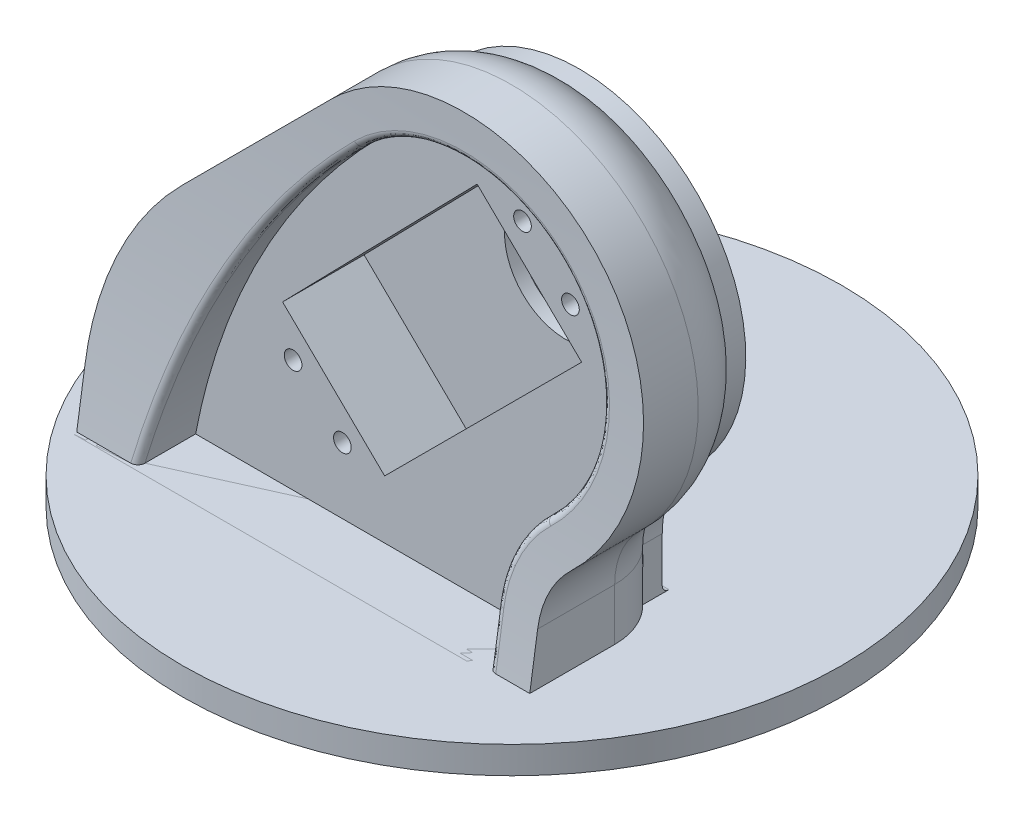
SolidWorks part; units mm, degrees
ref_plane "前视基准面" through (0, 0, 0) normal (0, 0, 1) x (1, 0, 0)
ref_plane "上视基准面" through (0, 0, 0) normal (0, 1, 0) x (1, 0, 0)
ref_plane "右视基准面" through (0, 0, 0) normal (1, 0, 0) x (0, 0, -1)
sketch "草图1" plane through (0, 0, 0) normal (0, 1, 0) x (1, 0, 0)
  line L0 (-7.25, 0) -> (14.0729, 0)
  circle A0 centre (0, 0) radius 48.5
  circle A1 centre (-7.25, 0) radius 1.5
  circle A2 centre (7.25, 0) radius 1.5
  dimension "D1" = 97
  dimension "D2" = 3
  dimension "D3" = 3
  dimension "D4" = 14.5
  dimension "D5" = 7.25
extrude "凸台-拉伸1" add sketch "草图1" along normal blind 4 contours A0 A2 A1 region at (-47.1282, 0, 0)
sketch "草图2" plane through (0, 0, 0) normal (0, -1, 0) x (1, 0, 0)
  circle A0 centre (0, 0) radius 3.75
  dimension "D1" = 7.5
extrude "切除-拉伸1" cut sketch "草图2" against normal blind 1.5
ref_plane "基准面1" through (0, 0, 4) normal (0, 0, 1) x (1, 0, 0)
sketch "草图3" plane through (0, 0, 4) normal (0, 0, 1) x (1, 0, 0)
  line L1 (-34.5671, 4) -> (-34.5671, 11.86)
  line L2 (48.5, 4) -> (-48.5, 4) construction
  line L3 (-24.2495, 36.7687) -> (-3.4141, 57.6041)
  line L5 (26.1129, 4) -> (-34.5671, 4)
  line L6 (26.1129, 11.64) -> (26.1129, 4)
  arc A0 (-34.5671, 11.86) -> (-24.2495, 36.7687) centre (0.6592, 11.86) cw
  arc A1 (-3.4141, 57.6041) -> (30.7827, 22.5159) centre (13.91, 40.28) cw
  arc A2 (30.7827, 22.5159) -> (26.1129, 11.64) centre (41.1129, 11.64) ccw
  circle A3 centre (13.91, 40.28) radius 9
  dimension "D6" = 24.5
  dimension "D7" = 15
  dimension "D9" = 18
  dimension "D1" = 7.86
  dimension "D2" = 7.64
  dimension "D3" = 40.28
  dimension "D4" = 13.91
  dimension "D5" = 45
  dimension "D8" = 60.68
extrude "凸台-拉伸2" add sketch "草图3" along normal blind 14
ref_plane "基准面2" through (0, 0, 6) normal (0, 0, 1) x (1, 0, 0)
sketch "草图4" plane through (0, 0, 6) normal (0, 0, 1) x (1, 0, 0)
  line L0 (12.8696, 56.5659) -> (28.25, 41.5516)
  line L1 (12.8696, 56.5659) -> (-15.7705, 27.2274)
  line L2 (28.25, 41.5516) -> (-0.7435, 12.5581)
  line L3 (-15.7705, 27.2274) -> (-0.7435, 12.5581)
  line L4 (12.8696, 56.5659) -> (13.2313, 41.5516) construction
  line L5 (13.2313, 41.5516) -> (28.25, 41.5516) construction
  line L6 (13.2313, 41.5516) -> (20.5598, 49.0587) construction
  line L7 (48.5, 4) -> (-48.5, 4) construction
  line L8 (19.5465, 55.1785) -> (26.6025, 48.091) construction
  line L9 (20.5598, 49.0587) -> (24.743, 53.3439) construction
  line L10 (-1.4504, 41.8967) -> (13.7532, 27.0548) construction
  circle A0 centre (19.5465, 55.1785) radius 1.3
  circle A1 centre (26.6025, 48.091) radius 1.3
  circle A2 centre (-6.9674, 13.7026) radius 1.3
  circle A3 centre (-14.2228, 20.5859) radius 1.3
  point P13 (23.0745, 51.6348)
  dimension "D8" = 2.6
  dimension "D9" = 2.6
  dimension "D1" = 91.38
  dimension "D2" = 45
  dimension "D3" = 41
  dimension "D4" = 21
  dimension "D5" = 5
  dimension "D6" = 5
  dimension "D7" = 3.6
extrude "切除-拉伸2" cut sketch "草图4" along normal through all
sketch "草图5" plane through (0, 0, 18) normal (0, 0, 1) x (1, 0, 0)
  line L0 (-5.5354, 59.7254) -> (-26.3708, 38.89)
  line L1 (-37.5671, 11.86) -> (-37.5671, 1)
  line L2 (-37.5671, 1) -> (29.1129, 1)
  line L3 (29.1129, 1) -> (29.1129, 6.5935)
  line L4 (-34.5671, 4) -> (26.1129, 4)
  line L5 (26.1129, 4) -> (26.1129, 11.64)
  line L6 (-3.4141, 57.6041) -> (-24.2495, 36.7687)
  line L7 (-34.5671, 11.86) -> (-34.5671, 4)
  line L8 (-28.5671, 4) -> (23.1129, 4)
  line L12 (-1.2928, 55.4828) -> (-22.1282, 34.6474) construction
  line L13 (-31.5671, 11.86) -> (-31.5671, 7) construction
  line L15 (23.1129, 7) -> (23.1129, 11.64)
  line L16 (-31.5671, 7) -> (-31.5671, 4) construction
  line L17 (23.1129, 7) -> (23.1129, 4)
  line L18 (26.1129, 4) -> (26.1129, 11.64) construction
  line L19 (29.1129, 1) -> (29.1129, 11.64) construction
  line L20 (-34.5671, 4) -> (26.1129, 4) construction
  line L21 (-3.4141, 57.6041) -> (-24.2495, 36.7687) construction
  line L22 (-34.5671, 11.86) -> (-34.5671, 4) construction
  line L23 (-31.5671, 7) -> (23.1129, 7) construction
  line L24 (29.1129, 6.5935) -> (29.1129, 11.64)
  arc A0 (-26.3708, 38.89) -> (-37.5671, 11.86) centre (0.6592, 11.86) ccw
  arc A1 (32.8488, 20.3408) -> (29.1129, 11.64) centre (41.1129, 11.64) ccw
  arc A2 (32.8488, 20.3408) -> (-5.5354, 59.7254) centre (13.91, 40.28) ccw
  arc A3 (30.7827, 22.5159) -> (26.1129, 11.64) centre (41.1129, 11.64) ccw
  arc A4 (30.7827, 22.5159) -> (-3.4141, 57.6041) centre (13.91, 40.28) ccw
  arc A5 (-24.2495, 36.7687) -> (-34.5671, 11.86) centre (0.6592, 11.86) ccw
  arc A9 (-22.1282, 34.6474) -> (-31.5671, 11.86) centre (0.6592, 11.86) ccw construction
  arc A10 (28.7167, 24.6911) -> (23.1129, 11.64) centre (41.1129, 11.64) ccw
  arc A11 (28.7167, 24.6911) -> (-1.2928, 55.4828) centre (13.91, 40.28) ccw
  arc A12 (30.7827, 22.5159) -> (26.1129, 11.64) centre (41.1129, 11.64) ccw construction
  arc A13 (30.7827, 22.5159) -> (-3.4141, 57.6041) centre (13.91, 40.28) ccw construction
  arc A14 (-24.2495, 36.7687) -> (-34.5671, 11.86) centre (0.6592, 11.86) ccw construction
  arc A15 (-1.2928, 55.4828) -> (-28.5671, 4) centre (68.8139, -14.6239) ccw
  dimension "D4" = 3
  dimension "D1" = 0
  dimension "D2" = 3
  dimension "D3" = 3
extrude "凸台-拉伸3" add sketch "草图5" along normal blind 9 and the other way up to vertex (14 mm away) separate body other way up to point (30.7827, 22.516, 4)
sketch "草图6" plane through (0, 0, 0) normal (1, 0, 0) x (0, 0, -1)
  line L0 (-27, 20.3408) -> (-27, 11.64) construction
  line L1 (-27, 67.78) -> (-27, 20.3408) construction
  line L2 (-27, 20.3408) -> (-27, 11.64)
  line L3 (-27, 67.78) -> (-27, 20.3408)
  line L4 (-27, 11.64) -> (-27, 4)
  line L5 (-27, 4) -> (-26.5, 4)
  line L6 (48.5, 4) -> (-48.5, 4) construction
  line L7 (-27, 67.78) -> (-21, 67.78)
  spline S0 degree 3 poles (-21, 67.78) (-21, 52.1647) (-22.1997, 30.9176) (-26.5, 4) knots 0 0 0 0 1 1 1 1
  dimension "D2" = 6
  dimension "D1" = 0.5
extrude "切除-拉伸3" cut sketch "草图6" against normal through all both and the other way through all
fillet "圆角2" radius 10 4 edges at (29.1129, 6.32, 4) (-15.9531, 49.3077, 4) (-37.5671, 6.43, 4) (-34.6573, 26.4885, 4)
fillet "圆角3" radius 1 1 edges at (-4.2271, 4, 4)
fillet "圆角4" radius 1 4 edges at (24.1378, 17.627, 24.5149) (27.5971, 56.8605, 21.1875) (-14.2323, 39.5353, 22.1846)
